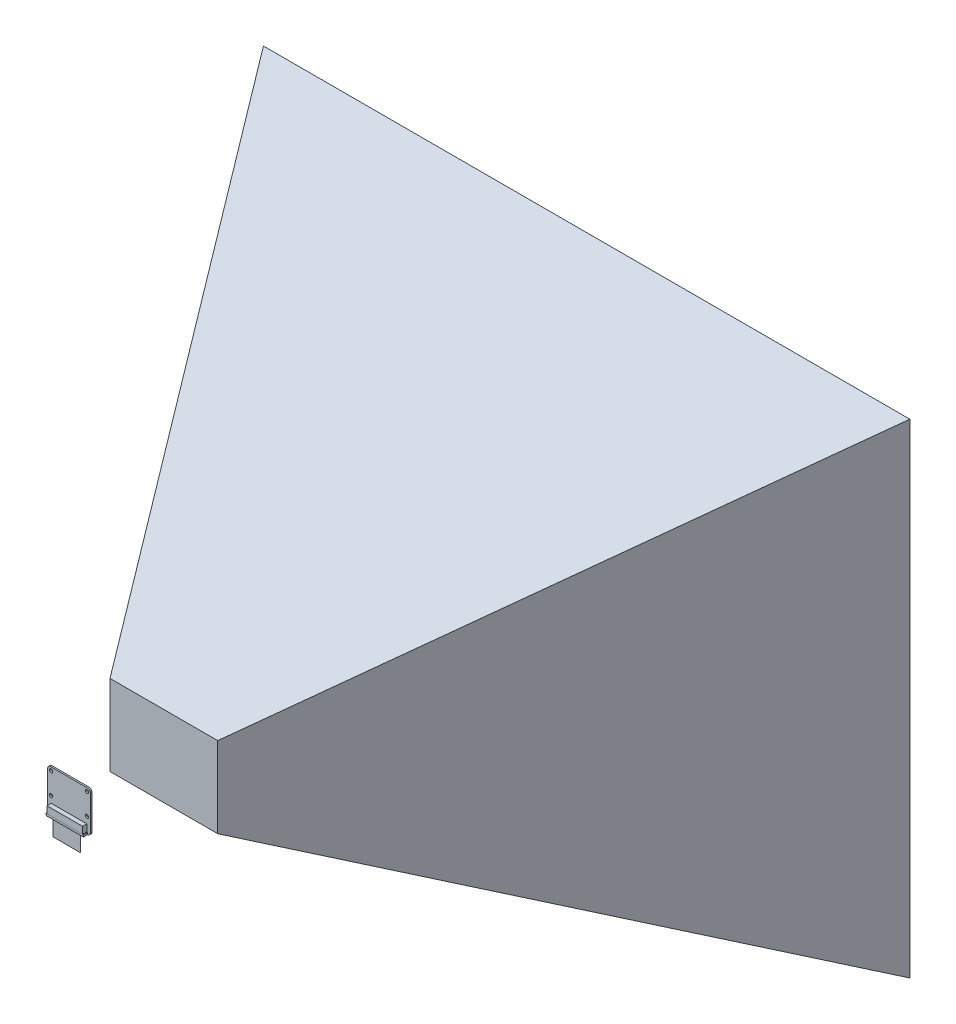
SolidWorks part; units mm, degrees
ref_plane "Front Plane" through (0, 0, 0) normal (0, 0, 1) x (1, 0, 0)
ref_plane "Top Plane" through (0, 0, 0) normal (0, 1, 0) x (1, 0, 0)
ref_plane "Right Plane" through (0, 0, 0) normal (1, 0, 0) x (0, 0, -1)
sketch "Sketch1" plane through (0, 0, 0) normal (0, 0, 1) x (1, 0, 0)
  line L0 (-12.6, 9.9) -> (12.6, 9.9) construction
  line L1 (-11.1, -11.9) -> (11.1, -11.9)
  line L2 (-12.6, -10.4) -> (-12.6, 10.4)
  line L3 (-11.1, 11.9) -> (11.1, 11.9)
  line L4 (12.6, -10.4) -> (12.6, 10.4)
  line L5 (-12.6, -11.9) -> (12.6, 11.9) construction
  line L6 (-12.6, 11.9) -> (12.6, -11.9) construction
  line L7 (-12.6, -2.8) -> (12.6, -2.8) construction
  line L8 (0, 11.9) -> (0, -11.9) construction
  line L10 (-4.3, -9.6) -> (4.3, -9.6)
  line L11 (-4.3, -9.6) -> (-4.3, -1)
  line L12 (-4.3, -1) -> (4.3, -1)
  line L13 (4.3, -9.6) -> (4.3, -1)
  line L14 (-4.3, -9.6) -> (4.3, -1) construction
  line L15 (-4.3, -1) -> (4.3, -9.6) construction
  circle A0 centre (10.6, 9.9) radius 1
  circle A1 centre (10.6, -2.8) radius 1
  circle A2 centre (-10.6, -2.8) radius 1
  circle A3 centre (-10.6, 9.9) radius 1
  arc A4 (-11.1, -11.9) -> (-12.6, -10.4) centre (-11.1, -10.4) cw
  arc A5 (11.1, -11.9) -> (12.6, -10.4) centre (11.1, -10.4) ccw
  arc A6 (-12.6, 10.4) -> (-11.1, 11.9) centre (-11.1, 10.4) cw
  arc A7 (11.1, 11.9) -> (12.6, 10.4) centre (11.1, 10.4) cw
  circle A8 centre (0, -5.3) radius 2.75
  circle A9 centre (0, -5.3) radius 0.65
  point P0 (0, 0)
  point P32 (0, -5.3)
  dimension "D3" = 2
  dimension "D8" = 1.5
  dimension "D11" = 5.5
  dimension "D12" = 1.3
  dimension "D1" = 25.2
  dimension "D2" = 23.8
  dimension "D4" = 2
  dimension "D5" = 2
  dimension "D6" = 2
  dimension "D7" = 9.1
  dimension "D9" = 8.6
  dimension "D10" = 10.9
extrude "Boss-Extrude1" add sketch "Sketch1" along normal blind 0.9 contours A7 L3 A6 L2 A4 L1 A5 L4 A2 A1 A0 L13 L10 L11 L12 A3 | L10 L13 L12 L11 | A8 A9 | A9 region at (0, 0.6794, 0) region at (-4.1784, -5.3, 0) region at (-2.6722, -5.3, 0) region at (0, -5.3, 0)
extrude "Boss-Extrude2" add sketch "Sketch1<3>" against normal blind 5.2 contours L10 L13 L12 L11 region at (-4.1784, -5.3, 0)
sketch "Sketch1<3>" plane through (0, 0, 0) normal (0, 0, 1) x (1, 0, 0) same geometry as "Sketch1"
extrude "Boss-Extrude3" add sketch "Sketch1<4>" against normal blind 5.2 separate body contours A8 A9 region at (-2.6722, -5.3, 0)
sketch "Sketch1<4>" plane through (0, 0, 0) normal (0, 0, 1) x (1, 0, 0) same geometry as "Sketch1"
extrude "Boss-Extrude4" add sketch "Sketch1<5>" against normal blind 5.2 separate body contours A9 region at (0, -5.3, 0)
sketch "Sketch1<5>" plane through (0, 0, 0) normal (0, 0, 1) x (1, 0, 0) same geometry as "Sketch1"
ref_plane "Plane2" through (0, 0, 0.9) normal (0, 0, 1) x (1, 0, 0)
sketch "Sketch3" plane through (0, 0, 0.9) normal (0, 0, 1) x (1, 0, 0)
  line L0 (0, 11.9) -> (0, -11.9) construction
  line L1 (-11.1, 11.9) -> (11.1, 11.9) construction
  line L2 (-11.1, -11.9) -> (11.1, -11.9) construction
  line L4 (-10.5, -10.8) -> (10.5, -10.8)
  line L5 (-10.5, -10.8) -> (-10.5, -6.7)
  line L6 (-10.5, -6.7) -> (10.5, -6.7)
  line L7 (10.5, -10.8) -> (10.5, -6.7)
  line L8 (-10.5, -10.8) -> (10.5, -6.7) construction
  line L9 (-10.5, -6.7) -> (10.5, -10.8) construction
  line L10 (11, -12) -> (-11, -12)
  line L11 (11, -12) -> (11, -10.8)
  line L12 (11, -10.8) -> (-11, -10.8)
  line L13 (-11, -12) -> (-11, -10.8)
  line L14 (11, -12) -> (-11, -10.8) construction
  line L15 (11, -10.8) -> (-11, -12) construction
  point P6 (0, -8.75)
  point P11 (0, -11.4)
  dimension "D1" = 21
  dimension "D2" = 4.1
  dimension "D3" = 1.2
  dimension "D4" = 22
  dimension "D5" = 0.1
extrude "Boss-Extrude5" add sketch "Sketch3" along normal blind 2.5 contours L4 L7 L6 L5 region at (0, -8.75, 0.9)
extrude "Boss-Extrude6" add sketch "Sketch3<3>" along normal blind 2.5 separate body contours L13 L10 L11 L12 L4 region at (0, -11.4, 0.9)
sketch "Sketch3<3>" plane through (0, 0, 0.9) normal (0, 0, 1) x (1, 0, 0) same geometry as "Sketch3"
ref_plane "Plane3" through (0, -12, 0) normal (0, -1, 0) x (-1, 0, 0)
sketch "Sketch4" plane through (0, -12, 0) normal (0, -1, 0) x (-1, 0, 0)
  line L0 (-11, -2.15) -> (11, -2.15) construction
  line L1 (-11, -3.4) -> (-11, -0.9) construction
  line L2 (11, -3.4) -> (11, -0.9) construction
  line L4 (8, -2.25) -> (-8, -2.25)
  line L5 (8, -2.25) -> (8, -2.05)
  line L6 (8, -2.05) -> (-8, -2.05)
  line L7 (-8, -2.25) -> (-8, -2.05)
  line L8 (8, -2.25) -> (-8, -2.05) construction
  line L9 (8, -2.05) -> (-8, -2.25) construction
  point P6 (0, -2.15)
  dimension "D1" = 16
  dimension "D2" = 0.2
extrude "Boss-Extrude7" add sketch "Sketch4" along normal blind 10
ref_point "Camera Center"
ref_plane "Camera Horizontal Plane" through (0, -5.3, 0) normal (0, 1, 0) x (1, 0, 0)
ref_plane "Camera Vertical Plane" through (0, 0, 0) normal (1, 0, 0) x (0, 0, -1)
sketch "Horizontal FoV" plane through (0, -5.3, 0) normal (0, 1, 0) x (1, 0, 0)
  line L0 (0, 5.2) -> (-191.1211, 305.2) construction
  line L1 (-191.1211, 305.2) -> (191.1211, 305.2)
  line L2 (191.1211, 305.2) -> (0, 5.2) construction
  line L3 (0, 5.2) -> (0, 5.4603) construction
  line L4 (-191.1211, 305.2) -> (-31.8535, 55.2)
  line L5 (-31.8535, 55.2) -> (31.8535, 55.2)
  line L6 (31.8535, 55.2) -> (191.1211, 305.2)
  point P5 (0, 305.2)
  dimension "D1" = 65
  dimension "D2" = 300
  dimension "D3" = 50
sketch "Vertical FoV" plane through (0, 0, 0) normal (1, 0, 0) x (0, 0, -1)
  line L0 (5.2, -5.3) -> (8.373, -5.3) construction
  line L1 (5.2, -5.3) -> (305.2, 137.7927) construction
  line L2 (5.2, -5.3) -> (305.2, -148.3927) construction
  line L3 (305.2, 137.7927) -> (305.2, -148.3927)
  line L4 (305.2, -148.3927) -> (55.2, -29.1488)
  line L5 (55.2, -29.1488) -> (55.2, 18.5488)
  line L6 (55.2, 18.5488) -> (305.2, 137.7927)
  point P6 (305.2, -5.3)
  dimension "D1" = 51
  dimension "D2" = 300
  dimension "D3" = 50
ref_plane "Plane6" through (0, 0, -55.2) normal (0, 0, 1) x (1, 0, 0)
sketch "Sketch7" plane through (0, 0, -55.2) normal (0, 0, 1) x (1, 0, 0)
  line L0 (-191.1211, -5.3) -> (191.1211, -5.3) construction
  line L1 (-31.8535, -29.1488) -> (31.8535, -29.1488)
  line L2 (-31.8535, -29.1488) -> (-31.8535, 18.5488)
  line L3 (-31.8535, 18.5488) -> (31.8535, 18.5488)
  line L4 (31.8535, -29.1488) -> (31.8535, 18.5488)
  line L5 (-31.8535, -29.1488) -> (31.8535, 18.5488) construction
  line L6 (-31.8535, 18.5488) -> (31.8535, -29.1488) construction
  line L7 (-31.8535, -5.3) -> (31.8535, -5.3) construction
  line L8 (0, -29.1488) -> (0, 18.5488) construction
  point P0 (0, -5.3)
ref_plane "Plane7" through (0, 0, -305.2) normal (0, 0, 1) x (1, 0, 0)
sketch "Sketch8" plane through (0, 0, -305.2) normal (0, 0, 1) x (1, 0, 0)
  line L0 (-191.1211, -5.3) -> (191.1211, -5.3) construction
  line L1 (-191.1211, -148.3927) -> (191.1211, -148.3927)
  line L2 (-191.1211, -148.3927) -> (-191.1211, 137.7927)
  line L3 (-191.1211, 137.7927) -> (191.1211, 137.7927)
  line L4 (191.1211, -148.3927) -> (191.1211, 137.7927)
  line L5 (-191.1211, -148.3927) -> (191.1211, 137.7927) construction
  line L6 (-191.1211, 137.7927) -> (191.1211, -148.3927) construction
  line L7 (0, 137.7927) -> (0, -148.3927) construction
  point P0 (0, -5.3)
loft "Camera FoV" add profiles "Sketch7", "Sketch8" connector at (-31.8535, -29.1488, -55.2) connector at (-191.1211, -148.3927, -305.2)
sketch "LED reference" plane through (0, 0, 0) normal (0, 0, -1) x (-1, 0, 0)
  line L0 (11.6, -2.8) -> (16.6, -2.8) construction
  line L1 (11.1, 11.9) -> (-11.1, 11.9) construction
  line L2 (-16.6, -11.9) -> (16.6, -11.9) construction
  line L3 (-16.6, -11.9) -> (-16.6, 11.9)
  line L4 (-16.6, 11.9) -> (16.6, 11.9) construction
  line L5 (16.6, -11.9) -> (16.6, 11.9)
  line L6 (-16.6, -11.9) -> (16.6, 11.9) construction
  line L7 (-16.6, 11.9) -> (16.6, -11.9) construction
  circle A0 centre (10.6, -2.8) radius 1 construction
  circle A1 centre (10.6, -2.8) radius 1 construction
  point P4 (0, 0)
  dimension "D1" = 5
sketch "Sketch9" plane through (0, 0, 0) normal (0, 0, -1) x (-1, 0, 0)
  line L0 (-12.6, -10.4) -> (-12.6, 10.4) construction
  line L1 (-6.4, 9) -> (2.9, 9)
  line L2 (-6.4, 9) -> (-6.4, 4.9)
  line L3 (-6.4, 4.9) -> (2.9, 4.9)
  line L4 (2.9, 9) -> (2.9, 4.9)
  line L5 (-6.4, 9) -> (2.9, 4.9) construction
  line L6 (-6.4, 4.9) -> (2.9, 9) construction
  line L7 (11.1, 11.9) -> (-11.1, 11.9) construction
  point P0 (-1.75, 6.95)
  dimension "D1" = 15.5
  dimension "D2" = 9.3
  dimension "D3" = 4.1
  dimension "D4" = 7
extrude "Boss-Extrude8" add sketch "Sketch9" along normal blind 1.5
